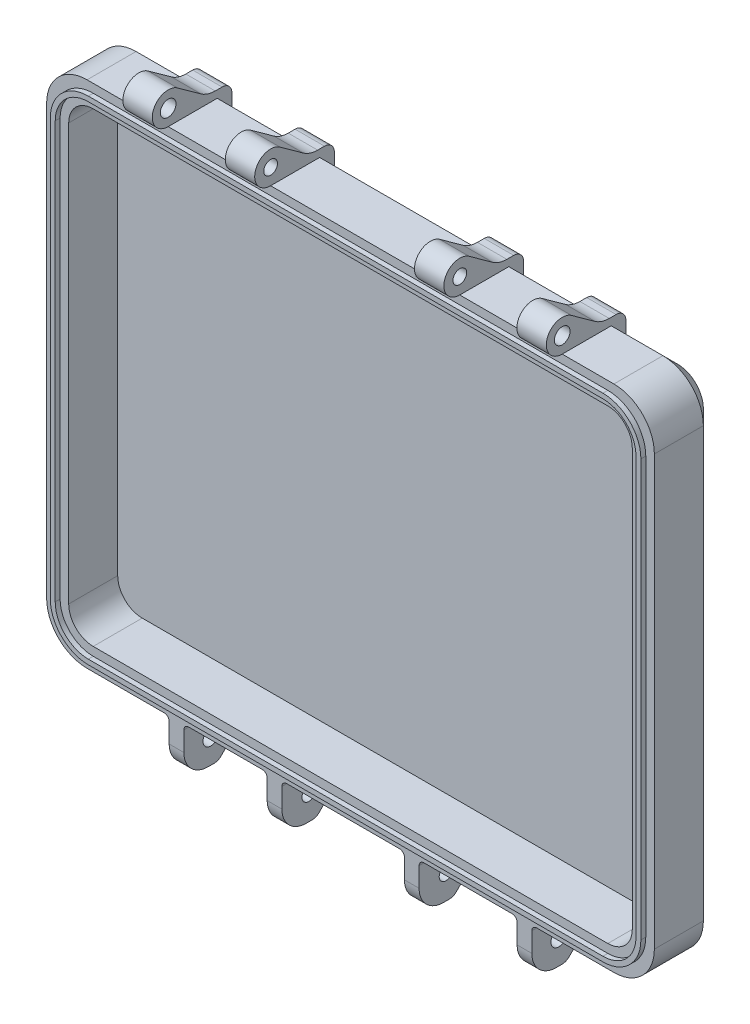
SolidWorks part; units mm, degrees
ref_plane "Front Plane" through (0, 0, 0) normal (0, 0, 1) x (1, 0, 0)
ref_plane "Top Plane" through (0, 0, 0) normal (0, 1, 0) x (1, 0, 0)
ref_plane "Right Plane" through (0, 0, 0) normal (1, 0, 0) x (0, 0, -1)
sketch "Sketch1" plane through (0, 0, 0) normal (0, 0, 1) x (1, 0, 0)
  line L1 (62, 52) -> (-62, 52)
  line L2 (62, 52) -> (62, -52)
  line L3 (62, -52) -> (-62, -52)
  line L4 (-62, 52) -> (-62, -52)
  line L5 (62, 52) -> (-62, -52) construction
  line L6 (62, -52) -> (-62, 52) construction
  line L7 (57.5, 47.5) -> (-57.5, 47.5)
  line L8 (57.5, 47.5) -> (57.5, -47.5)
  line L9 (57.5, -47.5) -> (-57.5, -47.5)
  line L10 (-57.5, 47.5) -> (-57.5, -47.5)
  line L11 (57.5, 47.5) -> (-57.5, -47.5) construction
  line L12 (57.5, -47.5) -> (-57.5, 47.5) construction
  point P0 (0, 0)
  point P6 (0, 0)
  dimension "D1" = 115
  dimension "D2" = 95
  dimension "D3" = 4.5
  dimension "D4" = 4.5
extrude "Boss-Extrude1" add sketch "Sketch1" along normal blind 10
extrude "Boss-Extrude2" add sketch "Sketch1<2>" against normal blind 3 contours L1 L4 L3 L2
sketch "Sketch1<2>" plane through (0, 0, 0) normal (0, 0, 1) x (1, 0, 0) same geometry as "Sketch1"
fillet "Fillet1" radius 8.25 4 edges at (62, -52, 3.5) (-62, -52, 3.5) (-62, 52, 3.5) (62, 52, 3.5)
fillet "Fillet2" radius 5 4 edges at (57.5, -47.5, 5) (-57.5, 47.5, 5) (-57.5, -47.5, 5) (57.5, 47.5, 5)
sketch "Sketch2" plane through (0, 0, 10) normal (0, 0, 1) x (1, 0, 0)
  line L3 (-52.5, 50.25) -> (52.5, 50.25)
  line L4 (-60.25, 42.5) -> (-60.25, -42.5)
  line L10 (-52.5, -50.25) -> (52.5, -50.25)
  line L13 (60.25, 42.5) -> (60.25, -42.5)
  line L14 (-60.25, 50.25) -> (60.25, -50.25) construction
  line L15 (-60.25, -50.25) -> (60.25, 50.25) construction
  line L16 (-52.5, 49.25) -> (52.5, 49.25)
  line L17 (-59.25, 42.5) -> (-59.25, -42.5)
  line L19 (-62, 43.75) -> (-62, -43.75) construction
  line L24 (52.5, 50.75) -> (-52.5, 50.75)
  line L25 (60.75, 42.5) -> (60.75, -42.5)
  line L30 (52.5, -50.75) -> (-52.5, -50.75)
  line L31 (-60.75, 42.5) -> (-60.75, -42.5)
  line L32 (60.75, 50.75) -> (-60.75, -50.75) construction
  line L33 (60.75, -50.75) -> (-60.75, 50.75) construction
  line L34 (52.5, 48.75) -> (-52.5, 48.75)
  line L35 (58.75, 42.5) -> (58.75, -42.5)
  line L36 (52.5, -48.75) -> (-52.5, -48.75)
  line L37 (-58.75, 42.5) -> (-58.75, -42.5)
  line L38 (58.75, 48.75) -> (-58.75, -48.75) construction
  line L39 (58.75, -48.75) -> (-58.75, 48.75) construction
  line L40 (-53.75, -52) -> (53.75, -52) construction
  line L41 (-52.5, -47.5) -> (52.5, -47.5) construction
  line L42 (-57.5, 42.5) -> (-57.5, -42.5) construction
  line L43 (-52.5, -49.25) -> (52.5, -49.25)
  line L44 (59.25, 42.5) -> (59.25, -42.5)
  line L45 (-59.25, 49.25) -> (59.25, -49.25) construction
  line L46 (-59.25, -49.25) -> (59.25, 49.25) construction
  arc A0 (-52.5, 50.25) -> (-60.25, 42.5) centre (-52.5, 42.5) ccw
  arc A5 (-60.25, -42.5) -> (-52.5, -50.25) centre (-52.5, -42.5) ccw
  arc A11 (52.5, 49.25) -> (59.25, 42.5) centre (52.5, 42.5) cw
  arc A16 (52.5, -50.25) -> (60.25, -42.5) centre (52.5, -42.5) ccw
  arc A17 (-52.5, -48.75) -> (-58.75, -42.5) centre (-52.5, -42.5) cw
  arc A18 (58.75, -42.5) -> (52.5, -48.75) centre (52.5, -42.5) cw
  arc A19 (52.5, 48.75) -> (58.75, 42.5) centre (52.5, 42.5) cw
  arc A20 (-52.5, 48.75) -> (-58.75, 42.5) centre (-52.5, 42.5) ccw
  arc A21 (60.75, -42.5) -> (52.5, -50.75) centre (52.5, -42.5) cw
  arc A22 (52.5, 50.75) -> (60.75, 42.5) centre (52.5, 42.5) cw
  arc A23 (-52.5, 50.75) -> (-60.75, 42.5) centre (-52.5, 42.5) ccw
  arc A24 (-52.5, -50.75) -> (-60.75, -42.5) centre (-52.5, -42.5) cw
  arc A25 (-52.5, 49.25) -> (-59.25, 42.5) centre (-52.5, 42.5) ccw
  arc A26 (-59.25, -42.5) -> (-52.5, -49.25) centre (-52.5, -42.5) ccw
  arc A27 (52.5, -49.25) -> (59.25, -42.5) centre (52.5, -42.5) ccw
  arc A28 (52.5, 50.25) -> (60.25, 42.5) centre (52.5, 42.5) cw
  point P0 (0, 0)
  point P5 (0, 0)
  point P36 (0, 0)
  point P41 (0, 0)
  dimension "D1" = 0.5
  dimension "D2" = 0.5
  dimension "D3" = 1.25
  dimension "D7" = 6.25
  dimension "D8" = 8.25
  dimension "D11" = 6.75
  dimension "D12" = 8.25
  dimension "D13" = 7.75
  dimension "D4" = 1.25
  dimension "D5" = 1.25
  dimension "D6" = 1.25
  dimension "D9" = 0.5
  dimension "D10" = 0.5
extrude "Boss-Extrude3" add sketch "Sketch2" along normal blind 1 contours A28 L3 A0 L4 A5 L10 A16 L13 A27 L43 A26 L17 A25 L16 A11 L44 region at (0, 50.0931, 10)
chamfer "Chamfer1" distance 3 angle 45 8 edges at (0, -52, -3) (59.5836, -49.5836, -3) (-59.5836, -49.5836, -3) (62, 0, -3) (-62, 0, -3) (59.5836, 49.5836, -3) (-59.5836, 49.5836, -3) (0, 52, -3)
sketch "Sketch3" plane through (-62, 0, 0) normal (-1, 0, 0) x (0, 0, 1)
  line L0 (10, 52) -> (-3, 52)
  line L1 (-3, 52) -> (-3, 49)
  line L2 (-3, 49) -> (-3, 43.75) construction
  line L3 (10, 52) -> (10, 55.25) construction
  line L4 (8.0993, 57.8862) -> (2.0156, 53.5)
  line L5 (2.0156, 53.5) -> (-3, 53.5)
  line L6 (-3, 53.5) -> (-3, 52)
  line L7 (-3, 49) -> (0, 52)
  circle A0 centre (10, 55.25) radius 3.25
  circle A1 centre (10, 55.25) radius 1.6
  circle A2 centre (10, 55.25) radius 1.4
  dimension "D2" = 3.25
  dimension "D3" = 6.5
  dimension "D6" = 3.2
  dimension "D7" = 2.8
  dimension "D1" = 3
  dimension "D4" = 7.5
  dimension "D5" = 1.5
extrude "Boss-Extrude4" add sketch "Sketch3" along normal blind 6 from offset 24.8 contours L1 L7 L0 | A0 L4 L5 L6 L0 | A0 A1 region at (-62, 53.4137, 3.5079) region at (-62, 54.2796, 6.9947) region at (-62, 51, -2) offset against normal yes
extrude "Boss-Extrude5" add sketch "Sketch3<4>" against normal blind 6 from offset 99.2 contours L1 L7 L0 | A0 L4 L5 L6 L0 | A0 A1 region at (-62, 53.4137, 3.5079) region at (-62, 54.2796, 6.9947) region at (-62, 51, -2) offset against normal yes
sketch "Sketch3<4>" plane through (-62, 0, 0) normal (-1, 0, 0) x (0, 0, 1) same geometry as "Sketch3"
extrude "Boss-Extrude6" add sketch "Sketch3<6>" against normal blind 6 from offset 39.7 contours A1 A2 | A0 A1 | A0 L4 L5 L6 L0 | L1 L7 L0 region at (-62, 53.4137, 3.5079) region at (-62, 54.2796, 6.9947) region at (-62, 51, -2) region at (-62, 55.25, 8.4453) offset against normal yes
sketch "Sketch3<6>" plane through (-62, 0, 0) normal (-1, 0, 0) x (0, 0, 1) same geometry as "Sketch3"
extrude "Boss-Extrude7" add sketch "Sketch3<7>" along normal blind 6 from offset 84.3 contours L1 L7 L0 | A0 L4 L5 L6 L0 | A0 A1 | A1 A2 region at (-62, 53.4137, 3.5079) region at (-62, 54.2796, 6.9947) region at (-62, 51, -2) region at (-62, 55.25, 8.4453) offset against normal yes
sketch "Sketch3<7>" plane through (-62, 0, 0) normal (-1, 0, 0) x (0, 0, 1) same geometry as "Sketch3"
fillet "Fillet3" radius 2 4 edges at (-40.2, 53.5, -3) (-19.3, 53.5, -3) (19.3, 53.5, -3) (40.2, 53.5, -3)
fillet "Fillet4" radius 5 4 edges at (-40.2, 53.5, 2.0156) (-19.3, 53.5, 2.0156) (19.3, 53.5, 2.0156) (40.2, 53.5, 2.0156)
sketch "Sketch4" plane through (62, 0, 0) normal (1, 0, 0) x (0, 0, -1)
  line L0 (3, -49) -> (3, -62)
  line L1 (3, -62) -> (-10, -62)
  line L2 (-10, -62) -> (-10, -52)
  line L3 (0, -52) -> (-10, -52) construction
  line L4 (-10, -57) -> (3, -57) construction
  line L5 (3, -49) -> (3, -43.75) construction
  line L6 (3, -49) -> (0, -52)
  line L7 (0, -52) -> (-10, -52)
  circle A0 centre (-4.5, -57) radius 1.6
  circle A1 centre (-4.5, -57) radius 1.4
  dimension "D3" = 3.2
  dimension "D5" = 2.8
  dimension "D1" = 10
  dimension "D2" = 10
  dimension "D4" = 7.5
extrude "Boss-Extrude8" add sketch "Sketch4" against normal blind 3 from offset 25 contours L2 L4 A0 L0 L6 L7 | L4 L2 L1 L0 A0 region at (62, -54.1476, 3.0606) region at (62, -59.6201, 3.4341) offset against normal yes
extrude "Boss-Extrude9" add sketch "Sketch4<3>" along normal blind 3 from offset 99 contours L2 L4 A0 L0 L6 L7 | L4 L2 L1 L0 A0 region at (62, -54.1476, 3.0606) region at (62, -59.6201, 3.4341) offset against normal yes
sketch "Sketch4<3>" plane through (62, 0, 0) normal (1, 0, 0) x (0, 0, -1) same geometry as "Sketch4"
extrude "Boss-Extrude10" add sketch "Sketch4<5>" against normal blind 3 from offset 48 contours L2 L4 A0 L0 L6 L7 | L4 L2 L1 L0 A0 | A0 L4 A1 | L4 A0 A1 region at (62, -54.1476, 3.0606) region at (62, -59.6201, 3.4341) region at (62, -58.5642, 4.5) region at (62, -56.9642, 3) offset against normal yes
sketch "Sketch4<5>" plane through (62, 0, 0) normal (1, 0, 0) x (0, 0, -1) same geometry as "Sketch4"
extrude "Boss-Extrude11" add sketch "Sketch4<6>" along normal blind 3 from offset 79 contours L2 L4 A0 L0 L6 L7 | L4 L2 L1 L0 A0 | A0 L4 A1 | L4 A0 A1 region at (62, -54.1476, 3.0606) region at (62, -59.6201, 3.4341) region at (62, -58.5642, 4.5) region at (62, -56.9642, 3) offset against normal yes
sketch "Sketch4<6>" plane through (62, 0, 0) normal (1, 0, 0) x (0, 0, -1) same geometry as "Sketch4"
chamfer "Chamfer2" distance 6 angle 45 4 edges at (-35.5, -62, -3) (-15.5, -62, -3) (12.5, -62, -3) (35.5, -62, -3)
fillet "Fillet5" radius 5 4 edges at (-35.5, -62, 10) (-15.5, -62, 10) (12.5, -62, 10) (35.5, -62, 10)
fillet "Fillet6" radius 2 4 edges at (35.5, -62, 3) (12.5, -62, 3) (-15.5, -62, 3) (-35.5, -62, 3)
fillet "Fillet7" radius 1 16 edges at (-34, -52, 5) (-34, -50.5, -1.5) (-37, -52, 5) (-37, -50.5, -1.5) (-17, -52, 5) (-17, -50.5, -1.5) (-14, -50.5, -1.5) (-14, -52, 5) (11, -52, 5) (11, -50.5, -1.5) (14, -52, 5) (14, -50.5, -1.5) (34, -52, 5) (34, -50.5, -1.5) (37, -50.5, -1.5) (37, -52, 5)
fillet "Fillet8" radius 4 4 edges at (35.5, -56, -3) (12.5, -56, -3) (-15.5, -56, -3) (-35.5, -56, -3)
